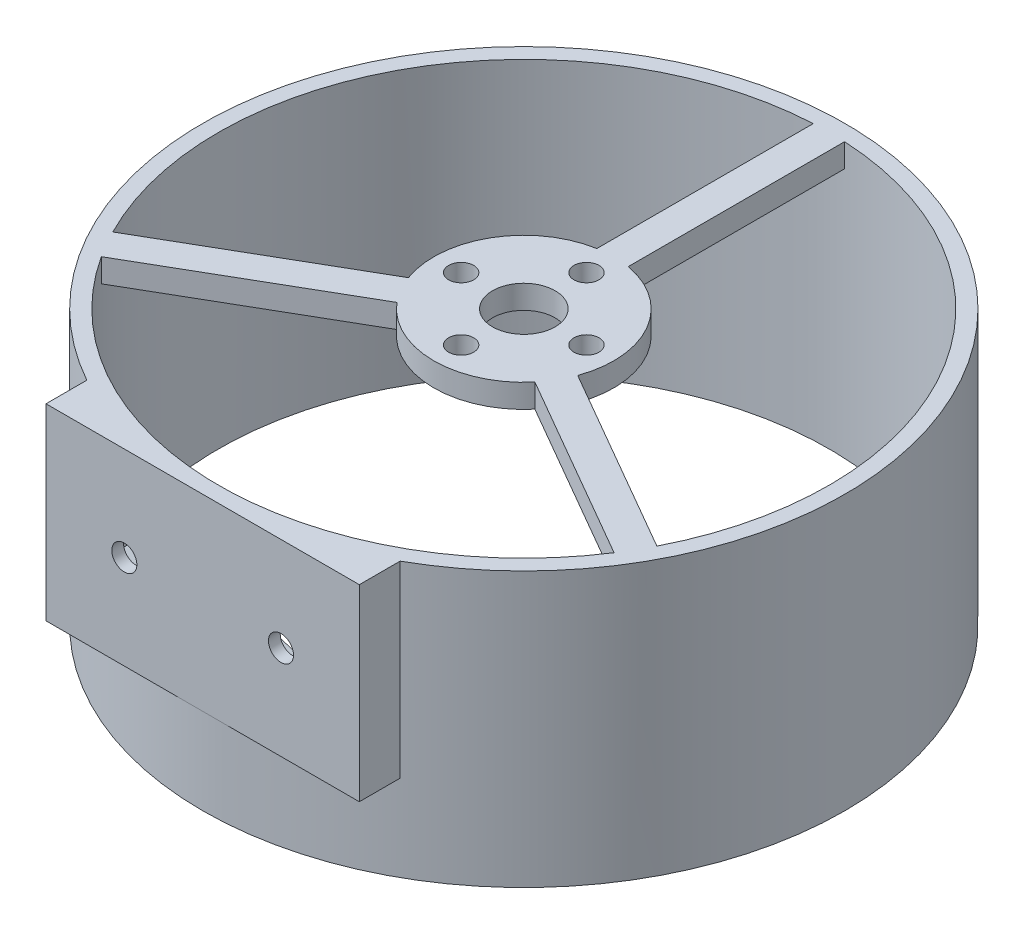
SolidWorks part; units mm, degrees
ref_plane "前视基准面" through (0, 0, 0) normal (0, 0, 1) x (1, 0, 0)
ref_plane "上视基准面" through (0, 0, 0) normal (0, 1, 0) x (1, 0, 0)
ref_plane "右视基准面" through (0, 0, 0) normal (1, 0, 0) x (0, 0, -1)
sketch "草图1" plane through (0, 0, 0) normal (0, 1, 0) x (1, 0, 0)
  circle A0 centre (0, 0) radius 39
  circle A1 centre (0, 0) radius 41
  dimension "D1" = 78
  dimension "D2" = 2
extrude "凸台-拉伸1" add sketch "草图1" along normal blind 20
sketch "草图2" plane through (0, 20, 0) normal (0, 1, 0) x (1, 0, 0)
  line L0 (20, -41) -> (-20, -41)
  line L1 (-20, -41) -> (-20, -35.7911)
  line L2 (0, -41) -> (0, -31.4417) construction
  line L3 (20, -41) -> (20, -35.7911)
  circle A0 centre (0, 0) radius 41 construction
  arc A1 (-20, -35.7911) -> (20, -35.7911) centre (0, 0) ccw
  circle M5 centre (0, 0) radius 41
extrude "凸台-拉伸2" add sketch "草图2" against normal blind 14 contours L1 L0 M5 | L0 L3 M5 region at (15.0657, 20, 39.4559) region at (-15.0657, 20, 39.4559)
sketch "草图3" plane through (0, 20, 0) normal (0, 1, 0) x (1, 0, 0)
  line L0 (-2, 38.9487) -> (-2, 11.3248)
  line L1 (0, 39) -> (0, 11.5) construction
  line L2 (2, 38.9487) -> (2, 11.3248)
  line L3 (34.7305, -17.7423) -> (10.8075, -3.9303)
  line L4 (32.7305, -21.2064) -> (8.8075, -7.3944)
  line L5 (-32.7305, -21.2064) -> (-8.8075, -7.3944)
  line L6 (-34.7305, -17.7423) -> (-10.8075, -3.9303)
  circle A0 centre (0, 0) radius 4
  circle A1 centre (-8, 0) radius 1.6
  circle A2 centre (8, 0) radius 1.6
  arc A3 (-8.8075, -7.3944) -> (8.8075, -7.3944) centre (0, 0) ccw
  circle A4 centre (0, 0) radius 39 construction
  arc A5 (2, 38.9487) -> (-2, 38.9487) centre (0, 0) ccw
  arc A6 (32.7305, -21.2064) -> (34.7305, -17.7423) centre (0, 0) ccw
  arc A7 (-34.7305, -17.7423) -> (-32.7305, -21.2064) centre (0, 0) ccw
  arc A8 (-2, 11.3248) -> (-10.8075, -3.9303) centre (0, 0) ccw
  arc A9 (10.8075, -3.9303) -> (2, 11.3248) centre (0, 0) ccw
  point P28 (0, 0)
  dimension "D1" = 8
  dimension "D2" = 3.2
  dimension "D3" = 8
  dimension "D4" = 3.2
  dimension "D5" = 8
  dimension "D6" = 23
  dimension "D7" = 2
  dimension "D8" = 3
extrude "凸台-拉伸3" add sketch "草图3" against normal blind 3
sketch "草图4" plane through (0, 0, 41) normal (0, 0, 1) x (1, 0, 0)
  line L0 (20, 20) -> (-20, 20) construction
  line L1 (-10, 4.7668) -> (-7.2, 6.3834)
  line L2 (-7.2, 6.3834) -> (-7.2, 9.6166)
  line L3 (-7.2, 9.6166) -> (-10, 11.2332)
  line L4 (-10, 11.2332) -> (-12.8, 9.6166)
  line L5 (-12.8, 9.6166) -> (-12.8, 6.3834)
  line L6 (-12.8, 6.3834) -> (-10, 4.7668)
  line L7 (0, 0) -> (0, -4.0742) construction
  line L8 (12.8, 6.3834) -> (10, 4.7668)
  line L9 (12.8, 9.6166) -> (12.8, 6.3834)
  line L10 (10, 11.2332) -> (12.8, 9.6166)
  line L11 (7.2, 9.6166) -> (10, 11.2332)
  line L12 (7.2, 6.3834) -> (7.2, 9.6166)
  line L13 (10, 4.7668) -> (7.2, 6.3834)
  circle A0 centre (-10, 8) radius 2.8 construction
  dimension "D1" = 5.6
  dimension "D2" = 10
  dimension "D3" = 12
sketch "草图7" plane through (0, 6, 0) normal (0, -1, 0) x (1, 0, 0)
  line L2 (-20, 41) -> (-20, 35.7911)
  line L3 (0, 41) -> (-20, 41)
  line L4 (-20, 41) -> (-20, 35.7911)
  line L5 (0, 41) -> (-20, 41)
  line L6 (20, 41) -> (0, 41)
  line L7 (20, 35.7911) -> (20, 41)
  line L8 (20, 41) -> (0, 41)
  line L9 (20, 35.7911) -> (20, 41)
  arc A1 (0, 41) -> (-20, 35.7911) centre (0, 0) ccw
  arc A2 (0, 41) -> (-20, 35.7911) centre (0, 0) ccw
  arc A3 (20, 35.7911) -> (0, 41) centre (0, 0) ccw
  arc A4 (20, 35.7911) -> (0, 41) centre (0, 0) ccw
  line M7 (-20, 41) -> (-20, 35.7911)
  arc M8 (-20, 35.7911) -> (0, 41) centre (0, 0) cw
  line M9 (0, 41) -> (-20, 41)
  dimension "D1" = 0
  dimension "D2" = 0
extrude "切除-拉伸3" cut sketch "草图7" against normal blind 3 contours M9 M7 M8 | A4 L9 L8 region at (-15.0657, 6, 39.4559) region at (15.0657, 6, 39.4559)
sketch "草图9" plane through (0, 0, 0) normal (0, -1, 0) x (1, 0, 0)
sketch "草图10" plane through (0, 0, 0) normal (0, -1, 0) x (1, 0, 0)
sketch "草图11" plane through (0, 0, 0) normal (0, -1, 0) x (1, 0, 0)
sketch "草图12" plane through (0, 0, 0) normal (0, -1, 0) x (1, 0, 0)
  circle A2 centre (0.1979, 0.0085) radius 41.1981
extrude "凸台-拉伸5" add sketch "草图1<2>" along normal blind 10 and the other way blind 15
sketch "草图1<2>" plane through (0, 0, 0) normal (0, 1, 0) x (1, 0, 0) same geometry as "草图1"
extrude "凸台-拉伸7" add sketch "草图7<4>" along normal blind 10
sketch "草图7<4>" plane through (0, 6, 0) normal (0, -1, 0) x (1, 0, 0) same geometry as "草图7"
extrude "凸台-拉伸8" add sketch "草图7<5>" along normal blind 10 and the other way blind 5 contours M9 M7 M8 | A4 L9 L8 region at (-15.0657, 6, 39.4559) region at (15.0657, 6, 39.4559)
sketch "草图7<5>" plane through (0, 6, 0) normal (0, -1, 0) x (1, 0, 0) same geometry as "草图7"
extrude "切除-拉伸4" cut sketch "草图4" against normal blind 10
extrude "凸台-拉伸9" add sketch "草图4<3>" along normal blind 10 and the other way blind 1.5
sketch "草图4<3>" plane through (0, 0, 41) normal (0, 0, 1) x (1, 0, 0) same geometry as "草图4"
sketch "草图13" plane through (0, 0, 51) normal (0, 0, 1) x (1, 0, 0)
  line L0 (10, 11.2332) -> (7.2, 9.6166)
  line L1 (7.2, 9.6166) -> (7.2, 6.3834)
  line L2 (7.2, 6.3834) -> (10, 4.7668)
  line L3 (10, 4.7668) -> (12.8, 6.3834)
  line L4 (12.8, 6.3834) -> (12.8, 9.6166)
  line L5 (12.8, 9.6166) -> (10, 11.2332)
  line L6 (-10, 11.2332) -> (-12.8, 9.6166)
  line L7 (-12.8, 9.6166) -> (-12.8, 6.3834)
  line L8 (-12.8, 6.3834) -> (-10, 4.7668)
  line L9 (-10, 4.7668) -> (-7.2, 6.3834)
  line L10 (-7.2, 6.3834) -> (-7.2, 9.6166)
  line L11 (-7.2, 9.6166) -> (-10, 11.2332)
extrude "切除-拉伸6" cut sketch "草图13" against normal blind 10
sketch "草图16" plane through (0, 0, 41) normal (0, 0, 1) x (1, 0, 0)
  line L1 (0, 0) -> (0, 20) construction
  line L2 (20, 20) -> (-20, 20) construction
  line L3 (20, 20) -> (-20, 20) construction
  circle A0 centre (-10, 8) radius 1.6
  circle A1 centre (10, 8) radius 1.6
  dimension "D1" = 20
  dimension "D2" = 10
  dimension "D3" = 12
extrude "切除-拉伸7" cut sketch "草图16" against normal blind 3
sketch "草图18" plane through (0, 20, 0) normal (0, 1, 0) x (1, 0, 0)
  circle A1 centre (0, 8) radius 1.6
  circle A2 centre (0, -8) radius 1.6
  point P7 (0, 0)
extrude "切除-拉伸8" cut sketch "草图18" against normal blind 10 contours A1
extrude "切除-拉伸9" cut sketch "草图18<4>" against normal blind 10
sketch "草图18<4>" plane through (0, 20, 0) normal (0, 1, 0) x (1, 0, 0) same geometry as "草图18"
